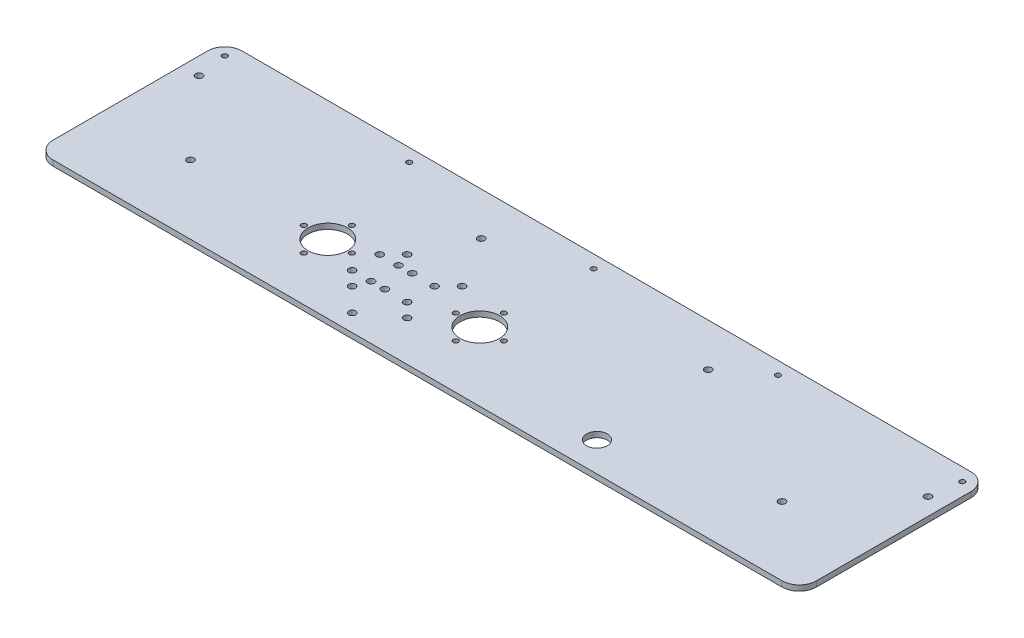
SolidWorks part; units mm, degrees
ref_plane "Front" through (0, 0, 0) normal (0, 0, 1) x (1, 0, 0)
ref_plane "Top" through (0, 0, 0) normal (0, 1, 0) x (1, 0, 0)
ref_plane "Right" through (0, 0, 0) normal (1, 0, 0) x (0, 0, -1)
sketch "Sketch1" plane through (0, 0, 0) normal (0, 1, 0) x (1, 0, 0)
  line L0 (-26.7996, 0) -> (-26.7996, 40)
  line L1 (-26.7996, 0) -> (417.7004, 0)
  line L2 (-26.7996, 0) -> (-26.7996, 110)
  line L3 (-26.7996, 110) -> (417.7004, 110)
  line L4 (417.7004, 0) -> (417.7004, 110)
  line L5 (-26.7996, 40) -> (23.2004, 40)
  line L6 (417.7004, 0) -> (417.7004, 40)
  line L7 (417.7004, 40) -> (367.7004, 40)
  line L8 (23.2004, 40) -> (103.2004, 40)
  line L9 (367.7004, 40) -> (191.7004, 40)
  line L10 (-26.7996, 110) -> (-26.7996, 85)
  line L11 (-26.7996, 85) -> (417.7004, 85)
  line L12 (-26.7996, 85) -> (-16.7996, 85)
  line L13 (417.7004, 85) -> (407.7004, 85)
  line L14 (103.2004, 40) -> (191.7004, 40)
  line L15 (147.4504, 40) -> (147.4504, 85)
  line L16 (279.7004, 40) -> (279.7004, 85)
  line L17 (147.4504, 40) -> (147.4504, 10)
  line L18 (-26.7996, 110) -> (-26.7996, 102.5)
  line L19 (-26.7996, 102.5) -> (417.7004, 102.5)
  line L20 (-26.7996, 102.5) -> (-19.2996, 102.5)
  line L21 (417.7004, 102.5) -> (410.2004, 102.5)
  line L22 (195.4504, 102.5) -> (410.2004, 102.5)
  line L23 (-19.2996, 102.5) -> (195.4504, 102.5)
  line L24 (417.7004, 0) -> (417.7004, 17.2282)
  line L25 (417.7004, 17.2282) -> (282.7004, 17.2282)
  circle A10 centre (367.7004, 40) radius 2
  circle A11 centre (23.2004, 40) radius 2
  circle A12 centre (103.2004, 40) radius 11.5
  circle A13 centre (103.2004, 40) radius 14
  circle A15 centre (103.2004, 54) radius 1.5
  circle A16 centre (89.2004, 40) radius 1.5
  circle A17 centre (103.2004, 26) radius 1.5
  circle A18 centre (117.2004, 40) radius 1.5
  circle A19 centre (191.7004, 40) radius 11.5
  circle A20 centre (191.7004, 40) radius 14
  circle A21 centre (191.7004, 26) radius 1.5
  circle A22 centre (205.7004, 40) radius 1.5
  circle A23 centre (191.7004, 54) radius 1.5
  circle A24 centre (177.7004, 40) radius 1.5
  circle A25 centre (-16.7996, 85) radius 2
  circle A26 centre (407.7004, 85) radius 2
  circle A27 centre (147.4504, 85) radius 2
  circle A28 centre (279.7004, 85) radius 2
  circle A29 centre (147.4504, 10) radius 2
  circle A30 centre (195.4504, 102.5) radius 1.5
  circle A31 centre (-19.2996, 102.5) radius 1.5
  circle A32 centre (410.2004, 102.5) radius 1.5
  circle A33 centre (302.8254, 102.5) radius 1.5
  circle A34 centre (88.0754, 102.5) radius 1.5
  circle A35 centre (282.7004, 17.2282) radius 6
  dimension "D3" = 40
  dimension "D7" = 80
  dimension "D8" = 176
  dimension "D9" = 25
  dimension "D11" = 10
  dimension "D12" = 30
  dimension "D13" = 7.5
  dimension "D14" = 7.5
  dimension "D16" = 17.2282
  dimension "D1" = 110
  dimension "D2" = 444.5
  dimension "D4" = 50
  dimension "D5" = 40
  dimension "D6" = 50
  dimension "D10" = 10
  dimension "D15" = 7.5
  dimension "D17" = 135
extrude "Boss-Extrude1" add sketch "Sketch1" along normal blind 3.175 contours A18 L14 A12 L8 A16 A13 A17 | A18 A13 A15 A16 L8 A12 L14 | A24 L14 A19 L9 A22 A20 A23 | A24 A20 A21 A22 L9 A19 L14 | A29 L14 A18 A13 A17 A16 L8 A11 L5 L0 L1 L4 L7 A10 L9 A22 A20 A21 A24 | A28 L11 A27 L15 L14 A24 A20 A23 A22 L9 L16 | A27 L11 A25 L2 L5 A11 L8 A16 A13 A15 A18 L14 L15 | A28 L11 A26 L13 L4 L3 L2 A25 A27 | A28 L16 L9 A10 L7 L4 L13 A26 L11 | A34 L23 A30 L22 A33 A32 L21 L4 L3 L10 L19 A31 region at (196.684, 0, -19.4923) region at (58.5861, 0, -63.184) region at (195.421, 0, -93.7571) region at (195.4504, 0, -106.2666) region at (348.6559, 0, -62.489) region at (93.521, 0, -49.6794) region at (90.515, 0, -38.754) region at (214.7998, 0, -63.4004) region at (204.3858, 0, -41.246) region at (201.3798, 0, -30.3206)
fillet "Fillet1" radius 10 4 edges at (417.7004, 1.5875, -110) (417.7004, 1.5875, 0) (-26.7996, 1.5875, 0) (-26.7996, 1.5875, -110)
sketch "Sketch2" plane through (0, 3.175, 0) normal (0, 1, 0) x (1, 0, 0)
  line L0 (-26.7996, 55.4056) -> (36.2004, 55.4056)
  line L1 (-26.7996, 10) -> (-26.7996, 100) construction
  line L2 (36.2004, 55.4056) -> (76.2004, 55.4056)
  line L3 (-16.7996, 110) -> (407.7004, 110) construction
  line L4 (36.2004, 55.4056) -> (36.2004, 23.4056)
  line L5 (36.2004, 23.4056) -> (68.2004, 23.4056)
  line L6 (76.2004, 55.4056) -> (165.9504, 55.4056)
  line L7 (165.9504, 55.4056) -> (133.9504, 55.4056)
  line L8 (133.9504, 55.4056) -> (133.9504, 23.4056)
  line L9 (133.9504, 23.4056) -> (165.9504, 23.4056)
  line L10 (133.9504, 23.4056) -> (125.9504, 23.4056)
  line L11 (125.9504, 23.4056) -> (125.9504, 55.4056)
  line L12 (165.9504, 55.4056) -> (157.9504, 55.4056)
  line L13 (157.9504, 55.4056) -> (157.9504, 23.4056)
  line L14 (157.9504, 23.4056) -> (157.9504, 31.4056)
  line L15 (157.9504, 55.4056) -> (157.9504, 47.4056)
  line L16 (157.9504, 47.4056) -> (133.9504, 47.4056)
  circle A4 centre (133.9504, 55.4056) radius 2
  circle A5 centre (165.9504, 55.4056) radius 2
  circle A9 centre (133.9504, 23.4056) radius 2
  circle A10 centre (165.9504, 23.4056) radius 2
  circle A11 centre (157.9504, 31.4056) radius 2
  circle A12 centre (125.9504, 31.4056) radius 2
  circle A13 centre (125.9504, 47.4056) radius 2
  circle A14 centre (157.9504, 47.4056) radius 2
  point P30 (0, 0)
  point P31 (0, 0)
  dimension "D5" = 89.75
  dimension "D6" = 32
  dimension "D7" = 8
  dimension "D10" = 8
  dimension "D1" = 63
  dimension "D2" = 40
  dimension "D3" = 54.5944
  dimension "D4" = 32
  dimension "D8" = 8
  dimension "D9" = 8
extrude "Cut-Extrude1" cut sketch "Sketch2" against normal blind 10 contours A4 | A5 | A13 | A12 | A9 | A10 | A11 | A14
sketch "Sketch3" plane through (0, 0, 0) normal (0, -1, 0) x (1, 0, 0)
  line L0 (133.9504, -55.4056) -> (133.9504, -47.4056)
  line L1 (133.9504, -47.4056) -> (136.9504, -47.4056)
  line L2 (136.9504, -47.4056) -> (144.9504, -47.4056)
  line L3 (136.9504, -47.4056) -> (136.9504, -31.4056)
  line L4 (136.9504, -31.4056) -> (144.9504, -31.4056)
  circle A0 centre (144.9504, -47.4056) radius 2
  circle A1 centre (136.9504, -47.4056) radius 2
  circle A2 centre (144.9504, -31.4056) radius 2
  circle A3 centre (136.9504, -31.4056) radius 2
  dimension "D3" = 8
  dimension "D1" = 3
  dimension "D2" = 8
  dimension "D4" = 16
extrude "Cut-Extrude2" cut sketch "Sketch3" against normal blind 10 contours L2 A1 L1 | L1 A1 L2 | A2 | L4 A3 L3 | L3 A1 L1 | L3 A3 L4 | A0 region at (136.1016, 0, -46.5568) region at (144.9504, 0, -29.4622) region at (136.6675, 0, -31.1227) region at (137.7992, 0, -32.2544) region at (136.9504, 0, -48.2544) region at (137.7992, 0, -46.5568)
